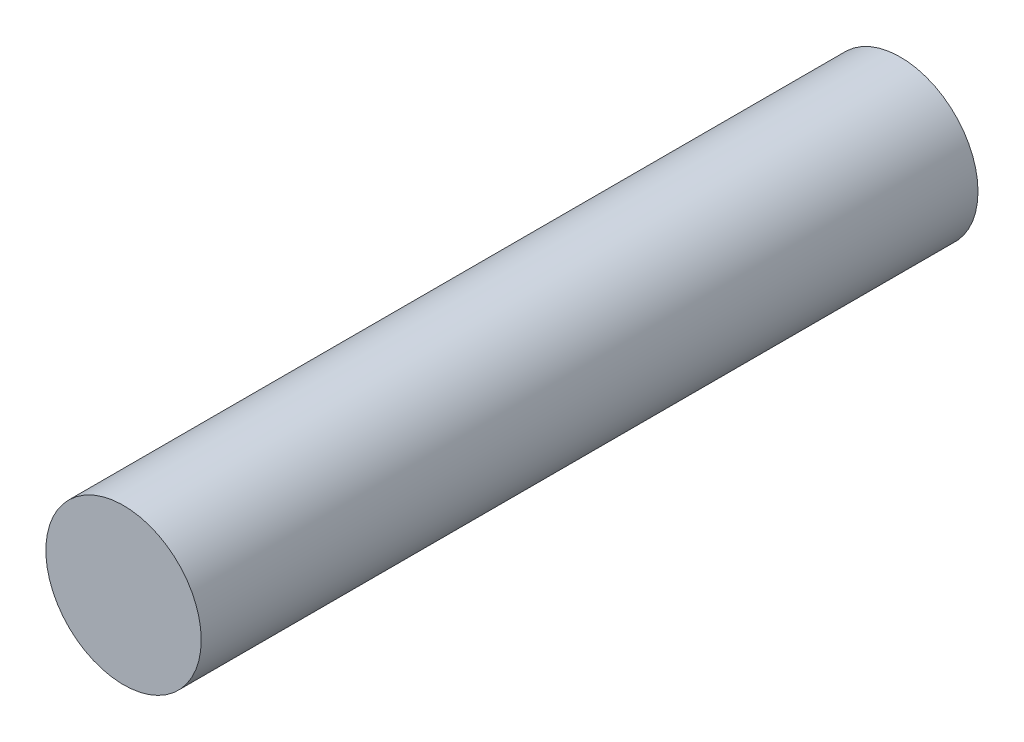
SolidWorks part; units mm, degrees
ref_plane "前视基准面" through (0, 0, 0) normal (0, 0, 1) x (1, 0, 0)
ref_plane "上视基准面" through (0, 0, 0) normal (0, 1, 0) x (1, 0, 0)
ref_plane "右视基准面" through (0, 0, 0) normal (1, 0, 0) x (0, 0, -1)
other "Configuration Table"
sketch "Sketch1" plane through (0, 0, 0) normal (0, 0, 1) x (1, 0, 0)
  circle A0 centre (0, 0) radius 15
extrude "Boss-Extrude1" add sketch "Sketch1" along normal blind 150
sketch3d "3DSketch1"
  line L0 (0, 0, 0) -> (0, 0, 150) construction
ref_axis "inner_tube_center_axis" through (0, 0, 0) along (0, 0, 1)
ref_plane "inner_tube_bottom_face" through (0, 0, 0) normal (0, 0, 1) x (1, 0, 0)
ref_plane "inner_tube_top_face" through (0, 0, 150) normal (0, 0, 1) x (1, 0, 0)
